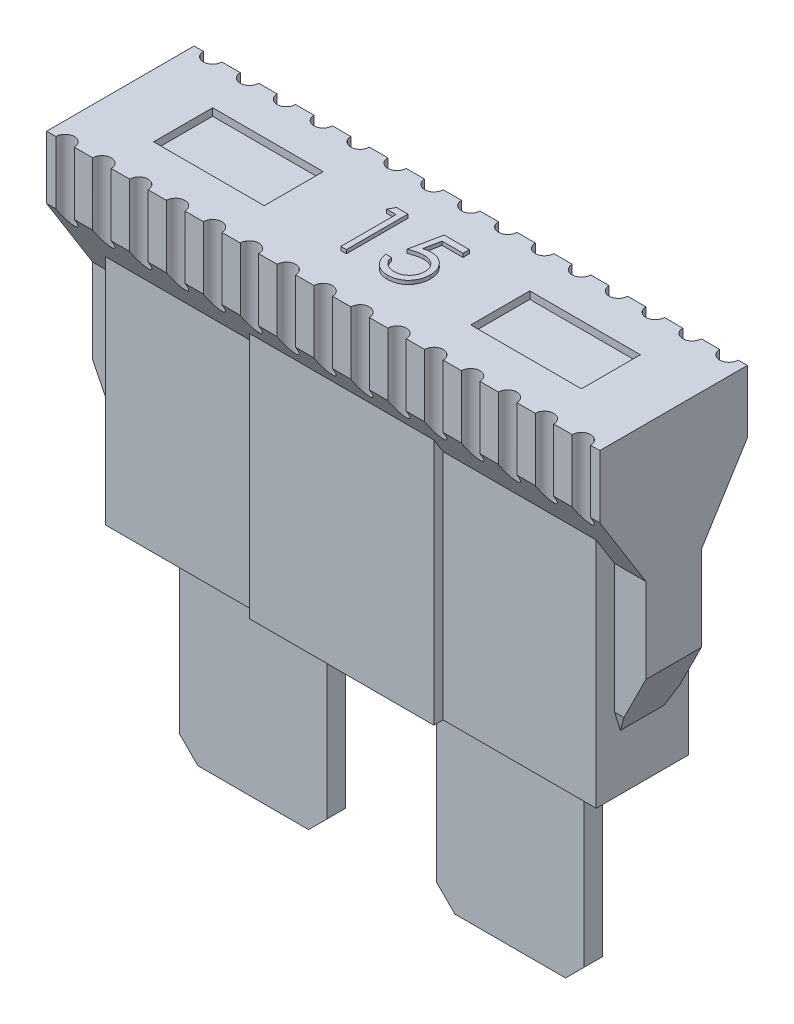
SolidWorks part; units mm, degrees
ref_plane "Front Plane" through (0, 0, 0) normal (0, 0, 1) x (1, 0, 0)
ref_plane "Top Plane" through (0, 0, 0) normal (0, 1, 0) x (1, 0, 0)
ref_plane "Right Plane" through (0, 0, 0) normal (1, 0, 0) x (0, 0, -1)
sketch "Sketch1" plane through (0, 0, 0) normal (1, 0, 0) x (0, 0, -1)
  line L0 (-2.54, 4.5531) -> (2.54, 4.5531)
  line L1 (2.54, 4.5531) -> (2.54, 2.3941)
  line L2 (2.54, 2.3941) -> (0.9525, -0.1459)
  line L3 (0.9525, -0.1459) -> (0.9525, -4.5798)
  line L4 (0.9525, -4.5798) -> (0.635, -5.6069)
  line L5 (0.635, -5.6069) -> (-0.635, -5.6069)
  line L6 (0, -5.6069) -> (0, 4.5531) construction
  line L7 (-0.9525, -4.5798) -> (-0.635, -5.6069)
  line L8 (-0.9525, -0.1459) -> (-0.9525, -4.5798)
  line L9 (-2.54, 2.3941) -> (-0.9525, -0.1459)
  line L10 (-2.54, 4.5531) -> (-2.54, 2.3941)
  point P2 (0.2203, -5.6069)
  dimension "D1" = 2.54
  dimension "D2" = 0.9525
  dimension "D3" = 0.9525
  dimension "D4" = 0.635
  dimension "D5" = 2.159
  dimension "D6" = 4.699
  dimension "D7" = 10.16
extrude "Boss-Extrude1" add sketch "Sketch1" along normal mid plane 19.05
sketch "Sketch2" plane through (0, 0, 0) normal (1, 0, 0) x (0, 0, -1)
  line L0 (1.5875, 0.8701) -> (1.5875, -7.1309)
  line L1 (0.9525, -0.1459) -> (2.54, 2.3941) construction
  line L2 (1.5875, -7.1309) -> (-1.5875, -7.1309)
  line L3 (-1.5875, -7.1309) -> (-1.5875, 0.8701)
  line L4 (-2.54, 2.3941) -> (-0.9525, -0.1459) construction
  line L5 (-1.5875, 0.8701) -> (1.5875, 0.8701)
  dimension "D1" = 8.001
  dimension "D2" = 3.175
extrude "Boss-Extrude2" add sketch "Sketch2" along normal mid plane 16.891
sketch "Sketch4" plane through (0, 4.5531, 0) normal (0, 1, 0) x (1, 0, 0)
  line L0 (9.525, 2.54) -> (-9.525, 2.54) construction
  line L1 (9.525, -2.54) -> (-9.525, -2.54) construction
  circle A0 centre (0, 2.54) radius 0.3175
  circle A1 centre (0, -2.54) radius 0.3175
  circle A2 centre (1.27, -2.54) radius 0.3175
  circle A3 centre (1.27, 2.54) radius 0.3175
  circle A4 centre (2.54, -2.54) radius 0.3175
  circle A5 centre (2.54, 2.54) radius 0.3175
  circle A6 centre (3.81, -2.54) radius 0.3175
  circle A7 centre (3.81, 2.54) radius 0.3175
  circle A8 centre (5.08, -2.54) radius 0.3175
  circle A9 centre (5.08, 2.54) radius 0.3175
  circle A10 centre (6.35, -2.54) radius 0.3175
  circle A11 centre (6.35, 2.54) radius 0.3175
  circle A12 centre (7.62, -2.54) radius 0.3175
  circle A13 centre (7.62, 2.54) radius 0.3175
  circle A14 centre (8.89, -2.54) radius 0.3175
  circle A15 centre (8.89, 2.54) radius 0.3175
  circle A16 centre (0, -2.54) radius 0.3175
  circle A17 centre (0, 2.54) radius 0.3175
  circle A18 centre (1.27, -2.54) radius 0.3175
  circle A19 centre (1.27, 2.54) radius 0.3175
  circle A20 centre (2.54, -2.54) radius 0.3175
  circle A21 centre (2.54, 2.54) radius 0.3175
  circle A22 centre (3.81, -2.54) radius 0.3175
  circle A23 centre (3.81, 2.54) radius 0.3175
  circle A24 centre (5.08, -2.54) radius 0.3175
  circle A25 centre (5.08, 2.54) radius 0.3175
  circle A26 centre (6.35, -2.54) radius 0.3175
  circle A27 centre (6.35, 2.54) radius 0.3175
  circle A28 centre (7.62, -2.54) radius 0.3175
  circle A29 centre (7.62, 2.54) radius 0.3175
  circle A30 centre (-1.27, -2.54) radius 0.3175
  circle A31 centre (-1.27, 2.54) radius 0.3175
  circle A32 centre (0, -2.54) radius 0.3175
  circle A33 centre (0, 2.54) radius 0.3175
  circle A34 centre (1.27, -2.54) radius 0.3175
  circle A35 centre (1.27, 2.54) radius 0.3175
  circle A36 centre (2.54, -2.54) radius 0.3175
  circle A37 centre (2.54, 2.54) radius 0.3175
  circle A38 centre (3.81, -2.54) radius 0.3175
  circle A39 centre (3.81, 2.54) radius 0.3175
  circle A40 centre (5.08, -2.54) radius 0.3175
  circle A41 centre (5.08, 2.54) radius 0.3175
  circle A42 centre (6.35, -2.54) radius 0.3175
  circle A43 centre (6.35, 2.54) radius 0.3175
  circle A44 centre (-2.54, -2.54) radius 0.3175
  circle A45 centre (-2.54, 2.54) radius 0.3175
  circle A46 centre (-1.27, -2.54) radius 0.3175
  circle A47 centre (-1.27, 2.54) radius 0.3175
  circle A48 centre (0, -2.54) radius 0.3175
  circle A49 centre (0, 2.54) radius 0.3175
  circle A50 centre (1.27, -2.54) radius 0.3175
  circle A51 centre (1.27, 2.54) radius 0.3175
  circle A52 centre (2.54, -2.54) radius 0.3175
  circle A53 centre (2.54, 2.54) radius 0.3175
  circle A54 centre (3.81, -2.54) radius 0.3175
  circle A55 centre (3.81, 2.54) radius 0.3175
  circle A56 centre (5.08, -2.54) radius 0.3175
  circle A57 centre (5.08, 2.54) radius 0.3175
  circle A58 centre (-3.81, -2.54) radius 0.3175
  circle A59 centre (-3.81, 2.54) radius 0.3175
  circle A60 centre (-2.54, -2.54) radius 0.3175
  circle A61 centre (-2.54, 2.54) radius 0.3175
  circle A62 centre (-1.27, -2.54) radius 0.3175
  circle A63 centre (-1.27, 2.54) radius 0.3175
  circle A64 centre (0, -2.54) radius 0.3175
  circle A65 centre (0, 2.54) radius 0.3175
  circle A66 centre (1.27, -2.54) radius 0.3175
  circle A67 centre (1.27, 2.54) radius 0.3175
  circle A68 centre (2.54, -2.54) radius 0.3175
  circle A69 centre (2.54, 2.54) radius 0.3175
  circle A70 centre (3.81, -2.54) radius 0.3175
  circle A71 centre (3.81, 2.54) radius 0.3175
  circle A72 centre (-5.08, -2.54) radius 0.3175
  circle A73 centre (-5.08, 2.54) radius 0.3175
  circle A74 centre (-3.81, -2.54) radius 0.3175
  circle A75 centre (-3.81, 2.54) radius 0.3175
  circle A76 centre (-2.54, -2.54) radius 0.3175
  circle A77 centre (-2.54, 2.54) radius 0.3175
  circle A78 centre (-1.27, -2.54) radius 0.3175
  circle A79 centre (-1.27, 2.54) radius 0.3175
  circle A80 centre (0, -2.54) radius 0.3175
  circle A81 centre (0, 2.54) radius 0.3175
  circle A82 centre (1.27, -2.54) radius 0.3175
  circle A83 centre (1.27, 2.54) radius 0.3175
  circle A84 centre (2.54, -2.54) radius 0.3175
  circle A85 centre (2.54, 2.54) radius 0.3175
  circle A86 centre (-6.35, -2.54) radius 0.3175
  circle A87 centre (-6.35, 2.54) radius 0.3175
  circle A88 centre (-5.08, -2.54) radius 0.3175
  circle A89 centre (-5.08, 2.54) radius 0.3175
  circle A90 centre (-3.81, -2.54) radius 0.3175
  circle A91 centre (-3.81, 2.54) radius 0.3175
  circle A92 centre (-2.54, -2.54) radius 0.3175
  circle A93 centre (-2.54, 2.54) radius 0.3175
  circle A94 centre (-1.27, -2.54) radius 0.3175
  circle A95 centre (-1.27, 2.54) radius 0.3175
  circle A96 centre (0, -2.54) radius 0.3175
  circle A97 centre (0, 2.54) radius 0.3175
  circle A98 centre (1.27, -2.54) radius 0.3175
  circle A99 centre (1.27, 2.54) radius 0.3175
  circle A100 centre (-7.62, -2.54) radius 0.3175
  circle A101 centre (-7.62, 2.54) radius 0.3175
  circle A102 centre (-6.35, -2.54) radius 0.3175
  circle A103 centre (-6.35, 2.54) radius 0.3175
  circle A104 centre (-5.08, -2.54) radius 0.3175
  circle A105 centre (-5.08, 2.54) radius 0.3175
  circle A106 centre (-3.81, -2.54) radius 0.3175
  circle A107 centre (-3.81, 2.54) radius 0.3175
  circle A108 centre (-2.54, -2.54) radius 0.3175
  circle A109 centre (-2.54, 2.54) radius 0.3175
  circle A110 centre (-1.27, -2.54) radius 0.3175
  circle A111 centre (-1.27, 2.54) radius 0.3175
  circle A112 centre (0, -2.54) radius 0.3175
  circle A113 centre (0, 2.54) radius 0.3175
  circle A114 centre (-1.27, -2.54) radius 0.3175
  circle A115 centre (-1.27, 2.54) radius 0.3175
  circle A116 centre (-2.54, -2.54) radius 0.3175
  circle A117 centre (-2.54, 2.54) radius 0.3175
  circle A118 centre (-3.81, -2.54) radius 0.3175
  circle A119 centre (-3.81, 2.54) radius 0.3175
  circle A120 centre (-5.08, -2.54) radius 0.3175
  circle A121 centre (-5.08, 2.54) radius 0.3175
  circle A122 centre (-6.35, -2.54) radius 0.3175
  circle A123 centre (-6.35, 2.54) radius 0.3175
  circle A124 centre (-7.62, -2.54) radius 0.3175
  circle A125 centre (-7.62, 2.54) radius 0.3175
  circle A126 centre (-8.89, -2.54) radius 0.3175
  circle A127 centre (-8.89, 2.54) radius 0.3175
  dimension "D1" = 0.635
  dimension "D2" = 8
  dimension "D3" = 8
extrude "Cut-Extrude1" cut sketch "Sketch4" against normal through all
sketch "Sketch5" plane through (0, -7.1309, 0) normal (0, -1, 0) x (1, 0, 0)
  line L1 (-3.175, 1.905) -> (3.175, 1.905)
  line L2 (-3.175, 1.905) -> (-3.175, -1.905)
  line L3 (-3.175, -1.905) -> (3.175, -1.905)
  line L4 (3.175, 1.905) -> (3.175, -1.905)
  line L5 (-3.175, 1.905) -> (3.175, -1.905) construction
  line L6 (-3.175, -1.905) -> (3.175, 1.905) construction
  point P0 (0, 0)
  dimension "D1" = 6.35
  dimension "D2" = 3.81
extrude "Boss-Extrude3" add sketch "Sketch5" against normal blind 9.271
sketch "Sketch6" plane through (0, 4.5531, 0) normal (0, 1, 0) x (1, 0, 0)
  line L0 (-9.525, 2.54) -> (-9.525, -2.54) construction
  line L1 (-7.366, 1.016) -> (-3.556, 1.016)
  line L2 (-7.366, 1.016) -> (-7.366, -1.016)
  line L3 (-7.366, -1.016) -> (-3.556, -1.016)
  line L4 (-3.556, 1.016) -> (-3.556, -1.016)
  line L5 (-7.366, 1.016) -> (-3.556, -1.016) construction
  line L6 (-7.366, -1.016) -> (-3.556, 1.016) construction
  line L7 (3.556, 1.016) -> (7.366, 1.016)
  line L8 (3.556, 1.016) -> (3.556, -1.016)
  line L9 (3.556, -1.016) -> (7.366, -1.016)
  line L10 (7.366, 1.016) -> (7.366, -1.016)
  line L11 (3.556, 1.016) -> (7.366, -1.016) construction
  line L12 (3.556, -1.016) -> (7.366, 1.016) construction
  line L13 (9.525, 2.54) -> (9.525, -2.54) construction
  point P0 (-5.461, 0)
  point P5 (5.461, 0)
  point P10 (0, 0)
  dimension "D1" = 3.81
  dimension "D2" = 2.032
  dimension "D3" = 2.159
  dimension "D4" = 2.159
extrude "Cut-Extrude2" cut sketch "Sketch6" against normal blind 0.254
sketch "Sketch7" plane through (0, -7.1309, 0) normal (0, -1, 0) x (1, 0, 0)
  line L1 (-7.1733, 0.3175) -> (-2.0933, 0.3175)
  line L2 (-7.1733, 0.3175) -> (-7.1733, -0.3175)
  line L3 (-7.1733, -0.3175) -> (-2.0933, -0.3175)
  line L4 (-2.0933, 0.3175) -> (-2.0933, -0.3175)
  line L5 (-7.1733, 0.3175) -> (-2.0933, -0.3175) construction
  line L6 (-7.1733, -0.3175) -> (-2.0933, 0.3175) construction
  line L7 (1.6777, 0.3175) -> (6.7577, 0.3175)
  line L8 (1.6777, 0.3175) -> (1.6777, -0.3175)
  line L9 (1.6777, -0.3175) -> (6.7577, -0.3175)
  line L10 (6.7577, 0.3175) -> (6.7577, -0.3175)
  line L11 (1.6777, 0.3175) -> (6.7577, -0.3175) construction
  line L12 (1.6777, -0.3175) -> (6.7577, 0.3175) construction
  point P0 (-4.6333, 0)
  point P5 (4.2177, 0)
  point P10 (0, 0)
  dimension "D1" = 5.08
  dimension "D2" = 0.635
extrude "Boss-Extrude4" add sketch "Sketch7" along normal blind 6.858 separate body
chamfer "Chamfer1" distance 0.635 angle 45 2 edges at (-2.0933, -13.9889, 0) (-7.1733, -13.9889, 0)
chamfer "Chamfer4" distance 0.635 angle 45 2 edges at (6.7577, -13.9889, 0) (1.6777, -13.9889, 0)
chamfer "Chamfer2" distance 2.54 distance2 1.27 1 edges at (-9.525, -5.6069, 0)
chamfer "Chamfer3" distance 1.27 distance2 2.54 1 edges at (9.525, -5.6069, 0)
sketch "Sketch8" plane through (0, 4.5531, 0) normal (0, 1, 0) x (1, 0, 0)
  line L0 (-3.556, -1.0369) -> (3.556, -1.0369) construction
  line L1 (-3.556, -1.016) -> (-3.556, 1.016) construction
  line L2 (3.556, 1.016) -> (3.556, -1.016) construction
  text T0 "15" font "Century Gothic" height in points 8
extrude "Boss-Extrude5" add sketch "Sketch8" along normal blind 0.127
sketch "Sketch10" plane through (0, -7.1309, 0) normal (0, 1, 0) x (1, 0, 0)
  line L1 (6.7577, 0.3175) -> (1.6777, 0.3175) construction
  line L3 (1.6777, -0.3175) -> (6.7577, -0.3175) construction
  line L5 (-2.0933, 0.3175) -> (-7.1733, 0.3175) construction
  line L7 (-7.1733, -0.3175) -> (-2.0933, -0.3175) construction
  line L9 (7.0117, 0.3175) -> (1.4237, 0.3175)
  line L11 (1.4237, -0.3175) -> (7.0117, -0.3175)
  line L13 (-1.8393, 0.3175) -> (-7.4273, 0.3175)
  line L15 (-7.4273, -0.3175) -> (-1.8393, -0.3175)
  line L16 (-7.4273, 0.3175) -> (-7.4273, -0.3175)
  line L17 (-1.8393, -0.3175) -> (-1.8393, 0.3175)
  line L18 (1.4237, 0.3175) -> (1.4237, -0.3175)
  line L19 (7.0117, -0.3175) -> (7.0117, 0.3175)
extrude "Boss-Extrude6" add sketch "Sketch10" along normal blind 8.89
sketch "Sketch12" plane through (0, 0, 0) normal (0, 0, 1) x (1, 0, 0)
  line L0 (-1.8358, -4.7271) -> (-1.8358, -5.2351)
  line L3 (1.4237, -4.7389) -> (1.4237, -5.2468)
  line L4 (1.4237, 1.7591) -> (1.4237, -7.1309) construction
  line L5 (0.8383, -1.1997) -> (0.8383, -4.1452)
  line L7 (-1.261, -1.1997) -> (-1.261, -4.1452)
  line L8 (0.3373, -1.1997) -> (0.3373, -4.1452)
  line L9 (-0.7459, -1.1997) -> (-0.7459, -4.1452)
  arc A3 (0.8383, -4.1452) -> (1.4237, -4.7389) centre (1.432, -4.1452) ccw
  arc A4 (0.8383, -1.1997) -> (-1.261, -1.1997) centre (-0.2113, -1.1997) ccw
  arc A5 (-1.8358, -4.7271) -> (-1.261, -4.1452) centre (-1.8429, -4.1452) ccw
  arc A6 (0.3373, -4.1452) -> (1.4237, -5.2468) centre (1.439, -4.1452) ccw
  arc A7 (0.3373, -1.1997) -> (-0.7459, -1.1997) centre (-0.2043, -1.1997) ccw
  arc A8 (-1.8358, -5.2351) -> (-0.7459, -4.1452) centre (-1.8358, -4.1452) ccw
  point P3 (0, 0)
  point P4 (0, 0)
extrude "Boss-Extrude7" add sketch "Sketch12" along normal mid plane 0.508 contours A4 L7 A5 L0 A8 L9 A7 L8 A6 L3 A3 L5
sketch "Sketch13" plane through (0, 0, 0.3175) normal (0, 0, 1) x (1, 0, 0)
  line L0 (-7.4273, 1.7591) -> (-1.8393, 1.7591) construction
  line L1 (-3.7443, 1.7591) -> (-1.8393, 1.7591)
  line L2 (-3.7443, 1.7591) -> (-3.7443, 0.4891)
  line L3 (-3.7443, 0.4891) -> (-1.8393, 0.4891)
  line L4 (-1.8393, 1.7591) -> (-1.8393, 0.4891)
  line L5 (-1.8393, 1.7591) -> (-1.8393, -7.1309) construction
  line L7 (1.4237, 1.7591) -> (3.3287, 1.7591)
  line L8 (1.4237, 1.7591) -> (1.4237, 0.4891)
  line L9 (1.4237, 0.4891) -> (3.3287, 0.4891)
  line L10 (3.3287, 1.7591) -> (3.3287, 0.4891)
  dimension "D1" = 1.905
  dimension "D2" = 1.27
extrude "Cut-Extrude3" cut sketch "Sketch13" against normal through all both and the other way through all
sketch "Sketch14" plane through (0, 0, 0.3175) normal (0, 0, 1) x (1, 0, 0)
  line L1 (-5.6914, -4.0066) -> (-3.4274, -4.0066)
  line L2 (-5.6914, -4.0066) -> (-5.6914, -5.8594)
  line L3 (-5.6914, -5.8594) -> (-3.4274, -5.8594)
  line L4 (-3.4274, -4.0066) -> (-3.4274, -5.8594)
  line L5 (-5.6914, -4.0066) -> (-3.4274, -5.8594) construction
  line L6 (-5.6914, -5.8594) -> (-3.4274, -4.0066) construction
  line L7 (3.0857, -4.0066) -> (5.3497, -4.0066)
  line L8 (3.0857, -4.0066) -> (3.0857, -5.8594)
  line L9 (3.0857, -5.8594) -> (5.3497, -5.8594)
  line L10 (5.3497, -4.0066) -> (5.3497, -5.8594)
  line L11 (3.0857, -4.0066) -> (5.3497, -5.8594) construction
  line L12 (3.0857, -5.8594) -> (5.3497, -4.0066) construction
  point P0 (-4.5594, -4.933)
  point P5 (4.2177, -4.933)
extrude "Cut-Extrude4" cut sketch "Sketch14" against normal through all
